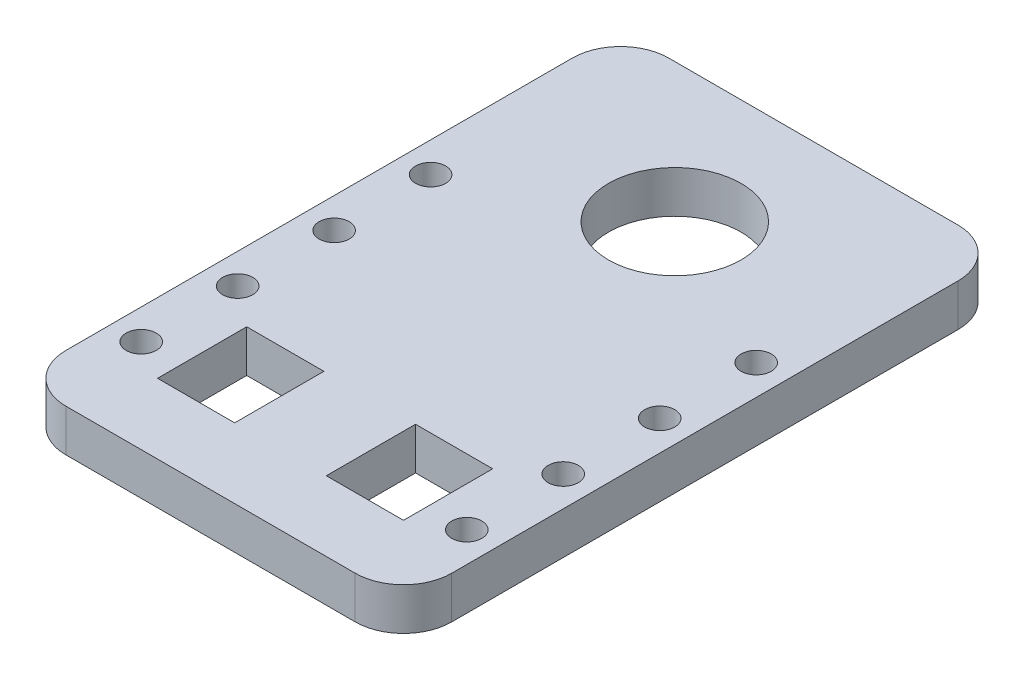
SolidWorks part; units mm, degrees
ref_plane "Plano frontal" through (0, 0, 0) normal (0, 0, 1) x (1, 0, 0)
ref_plane "Plano superior" through (0, 0, 0) normal (0, 1, 0) x (1, 0, 0)
ref_plane "Plano direito" through (0, 0, 0) normal (1, 0, 0) x (0, 0, -1)
sketch "Sketch1" plane through (0, 0, 0) normal (0, 1, 0) x (1, 0, 0)
  line L0 (-16, -25) -> (-16, -15.5) construction
  line L1 (-16, -25) -> (16, -25)
  line L2 (-16, -25) -> (-16, 25)
  line L3 (-16, 25) -> (16, 25)
  line L4 (16, -25) -> (16, 25)
  line L5 (-16, -25) -> (16, 25) construction
  line L6 (-16, 25) -> (16, -25) construction
  line L7 (-16, -15.5) -> (16, -15.5) construction
  line L8 (0, -15.5) -> (3.8, -15.5) construction
  line L9 (3.8, -15.5) -> (3.8, -11.8)
  line L10 (3.8, -11.8) -> (10.2, -11.8)
  line L11 (10.2, -11.8) -> (10.2, -19.2)
  line L12 (10.2, -19.2) -> (3.8, -19.2)
  line L13 (3.8, -19.2) -> (3.8, -15.5)
  line L15 (0, -55) -> (0, 55) construction
  line L16 (-10.2, -19.2) -> (-3.8, -19.2)
  line L17 (-10.2, -11.8) -> (-10.2, -19.2)
  line L18 (-3.8, -11.8) -> (-10.2, -11.8)
  line L19 (-3.8, -19.2) -> (-3.8, -15.5)
  line L20 (-3.8, -15.5) -> (-3.8, -11.8)
  line L21 (-16, 25) -> (-16, 13.5) construction
  line L22 (-16, 13.5) -> (16, 13.5) construction
  line L23 (0, 25) -> (0, 6.75) construction
  line L24 (0, 6.75) -> (13.5, 6.75) construction
  circle A0 centre (0, 13.5) radius 5.5
  circle A1 centre (13.5, 6.75) radius 1.25
  circle A2 centre (13.5, -1.25) radius 1.25
  circle A3 centre (13.5, -9.25) radius 1.25
  circle A4 centre (13.5, -17.25) radius 1.25
  circle A5 centre (-13.5, -17.25) radius 1.25
  circle A6 centre (-13.5, -9.25) radius 1.25
  circle A7 centre (-13.5, -1.25) radius 1.25
  circle A8 centre (-13.5, 6.75) radius 1.25
  point P0 (0, 0)
  dimension "D6" = 11
  dimension "D11" = 2.5
  dimension "D1" = 50
  dimension "D2" = 32
  dimension "D3" = 3.8
  dimension "D4" = 7.4
  dimension "D5" = 6.4
  dimension "D7" = 11.5
  dimension "D8" = 29
  dimension "D9" = 18.25
  dimension "D10" = 13.5
  dimension "D13" = 8
  dimension "D12" = 4
extrude "Boss-Extrude1" add sketch "Sketch1" along normal blind 3.5
fillet "Filete1" radius 4 4 edges at (16, 1.75, 25) (-16, 1.75, 25) (-16, 1.75, -25) (16, 1.75, -25)
